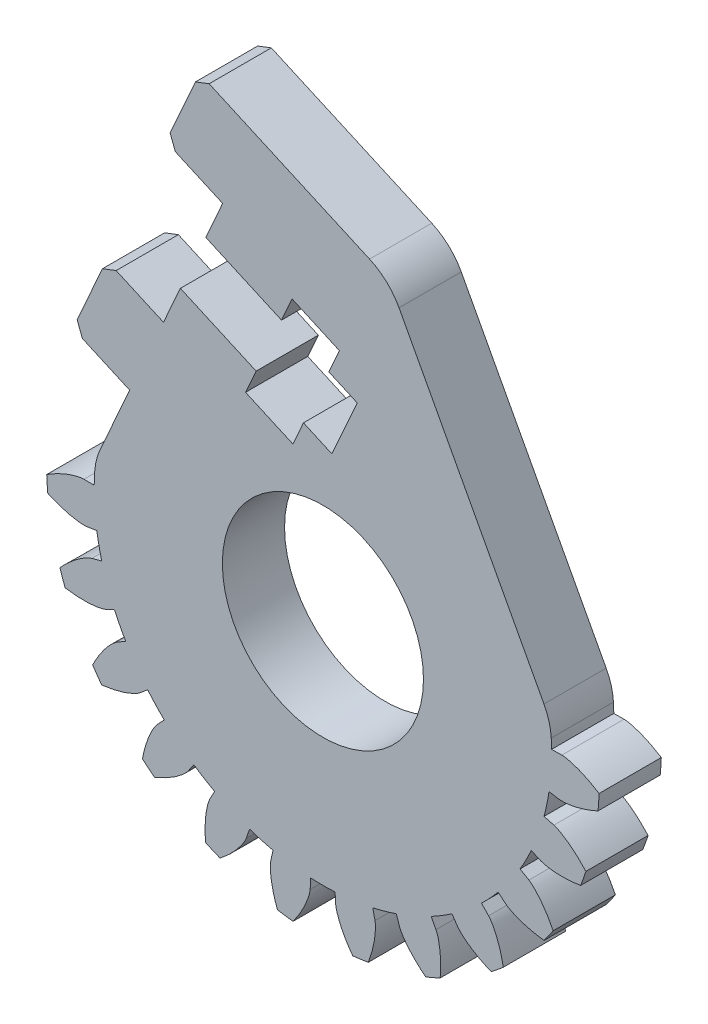
SolidWorks part; units mm, degrees
material "Lasercut ABS"
ref_plane "Front Plane" through (0, 0, 0) normal (0, 0, 1) x (1, 0, 0)
ref_plane "Top Plane" through (0, 0, 0) normal (0, 1, 0) x (1, 0, 0)
ref_plane "Right Plane" through (0, 0, 0) normal (1, 0, 0) x (0, 0, -1)
sketch "Model" plane through (0, 0, 0) normal (0, 0, 1) x (1, 0, 0)
  line L0 (-3.5387, -10.448) -> (-3.6973, -10.9162)
  line L1 (-5.4543, -10.153) -> (-5.2204, -9.7176)
  line L2 (-6.2264, -9.1058) -> (-6.5054, -9.5139)
  line L3 (-7.9913, -8.3049) -> (-7.6486, -7.9488)
  line L4 (-8.4522, -7.0883) -> (-8.8309, -7.4059)
  line L5 (-9.9356, -5.8409) -> (-9.5095, -5.5904)
  line L6 (-10.0512, -4.5451) -> (-10.5016, -4.7487)
  line L7 (-11.1431, -2.9437) -> (-10.6651, -2.8175)
  line L8 (-10.9047, -1.6648) -> (-11.3933, -1.7394)
  line L9 (-11.524, 0.1718) -> (-11.0298, 0.1644)
  line L10 (-10.9495, 1.339) -> (-11.4401, 1.399)
  line L11 (-11.0504, 3.2746) -> (-10.5764, 3.1341)
  line L12 (-10.1822, 4.2435) -> (-10.6384, 4.4336)
  line L13 (-9.7571, 6.1345) -> (-9.3387, 5.8714)
  line L14 (-8.6597, 6.8332) -> (-9.0477, 7.1394)
  line L15 (-7.7402, 8.5394) -> (-7.4083, 8.1732)
  line L16 (-6.495, 8.9162) -> (-6.786, 9.3157)
  line L17 (-5.1493, 10.3111) -> (-4.9285, 9.8688)
  line L18 (-3.8486, 10.3379) -> (-4.021, 10.8011)
  line L19 (-2.1765, 11.318) -> (-2.0831, 10.8326)
  line L20 (-0.9167, 10.9929) -> (-0.9578, 11.4855)
  line L21 (0.9578, 11.4855) -> (0.9167, 10.9929)
  line L22 (2.0831, 10.8326) -> (2.1765, 11.318)
  line L23 (4.021, 10.8011) -> (3.8486, 10.3379)
  line L24 (4.9285, 9.8688) -> (5.1493, 10.3111)
  line L25 (6.786, 9.3157) -> (6.495, 8.9162)
  line L26 (7.4083, 8.1732) -> (7.7402, 8.5394)
  line L27 (9.0477, 7.1394) -> (8.6597, 6.8332)
  line L28 (9.3387, 5.8714) -> (9.7571, 6.1345)
  line L29 (10.6384, 4.4336) -> (10.1822, 4.2435)
  line L30 (10.5764, 3.1341) -> (11.0504, 3.2746)
  line L31 (11.4401, 1.399) -> (10.9495, 1.339)
  line L32 (11.0298, 0.1644) -> (11.524, 0.1718)
  line L33 (11.3933, -1.7394) -> (10.9047, -1.6648)
  line L34 (10.6651, -2.8175) -> (11.1431, -2.9437)
  line L35 (10.5016, -4.7487) -> (10.0512, -4.5451)
  line L36 (9.5095, -5.5904) -> (9.9356, -5.8409)
  line L37 (8.8309, -7.4059) -> (8.4522, -7.0883)
  line L38 (7.6486, -7.9488) -> (7.9913, -8.3049)
  line L39 (6.5054, -9.5139) -> (6.2264, -9.1058)
  line L40 (5.2204, -9.7176) -> (5.4543, -10.153)
  line L41 (3.6973, -10.9162) -> (3.5387, -10.448)
  line L42 (2.405, -10.7657) -> (2.5128, -11.2481)
  line L43 (0.6151, -11.5089) -> (0.5887, -11.0153)
  line L44 (-0.5887, -11.0153) -> (-0.6151, -11.5089)
  line L45 (-2.5128, -11.2481) -> (-2.405, -10.7657)
  arc A0 (-5.6568, -12.0719) -> (-4.9615, -12.3739) centre (0, 0) ccw
  arc A1 (-6.2264, -9.1058) -> (-5.2204, -9.7176) centre (0, 0) ccw
  arc A2 (-8.704, -10.098) -> (-8.1159, -10.5765) centre (0, 0) ccw
  arc A3 (-8.4522, -7.0883) -> (-7.6486, -7.9488) centre (0, 0) ccw
  arc A4 (-11.1057, -7.3752) -> (-10.6684, -7.9946) centre (0, 0) ccw
  arc A5 (-10.0512, -4.5451) -> (-9.5095, -5.5904) centre (0, 0) ccw
  arc A6 (-12.6836, -4.1055) -> (-12.4297, -4.8198) centre (0, 0) ccw
  arc A7 (-10.9047, -1.6648) -> (-10.6651, -2.8175) centre (0, 0) ccw
  arc A8 (-13.3209, -0.5312) -> (-13.2692, -1.2876) centre (0, 0) ccw
  arc A9 (-10.9495, 1.339) -> (-11.0298, 0.1644) centre (0, 0) ccw
  arc A10 (-12.9703, 3.0824) -> (-13.1245, 2.3401) centre (0, 0) ccw
  arc A11 (-10.1822, 4.2435) -> (-10.5764, 3.1341) centre (0, 0) ccw
  arc A12 (-11.6577, 6.4675) -> (-12.0065, 5.7943) centre (0, 0) ccw
  arc A13 (-8.6597, 6.8332) -> (-9.3387, 5.8714) centre (0, 0) ccw
  arc A14 (-9.4805, 9.3728) -> (-9.998, 8.8187) centre (0, 0) ccw
  arc A15 (-6.495, 8.9162) -> (-7.4083, 8.1732) centre (0, 0) ccw
  arc A16 (-6.6002, 11.5831) -> (-7.2479, 11.1891) centre (0, 0) ccw
  arc A17 (-3.8486, 10.3379) -> (-4.9285, 9.8688) centre (0, 0) ccw
  arc A18 (-3.2303, 12.9342) -> (-3.9604, 12.7297) centre (0, 0) ccw
  arc A19 (-0.9167, 10.9929) -> (-2.0831, 10.8326) centre (0, 0) ccw
  arc A20 (0.3791, 13.3261) -> (-0.3791, 13.3261) centre (0, 0) ccw
  arc A21 (2.0831, 10.8326) -> (0.9167, 10.9929) centre (0, 0) ccw
  arc A22 (3.9604, 12.7297) -> (3.2303, 12.9342) centre (0, 0) ccw
  arc A23 (4.9285, 9.8688) -> (3.8486, 10.3379) centre (0, 0) ccw
  arc A24 (7.2479, 11.1891) -> (6.6002, 11.5831) centre (0, 0) ccw
  arc A25 (7.4083, 8.1732) -> (6.495, 8.9162) centre (0, 0) ccw
  arc A26 (9.998, 8.8187) -> (9.4805, 9.3728) centre (0, 0) ccw
  arc A27 (9.3387, 5.8714) -> (8.6597, 6.8332) centre (0, 0) ccw
  arc A28 (12.0065, 5.7943) -> (11.6577, 6.4675) centre (0, 0) ccw
  arc A29 (10.5764, 3.1341) -> (10.1822, 4.2435) centre (0, 0) ccw
  arc A30 (13.1245, 2.3401) -> (12.9703, 3.0824) centre (0, 0) ccw
  arc A31 (11.0298, 0.1644) -> (10.9495, 1.339) centre (0, 0) ccw
  arc A32 (13.2692, -1.2876) -> (13.3209, -0.5312) centre (0, 0) ccw
  arc A33 (10.6651, -2.8175) -> (10.9047, -1.6648) centre (0, 0) ccw
  arc A34 (12.4297, -4.8198) -> (12.6836, -4.1055) centre (0, 0) ccw
  arc A35 (9.5095, -5.5904) -> (10.0512, -4.5451) centre (0, 0) ccw
  arc A36 (10.6684, -7.9946) -> (11.1057, -7.3752) centre (0, 0) ccw
  arc A37 (7.6486, -7.9488) -> (8.4522, -7.0883) centre (0, 0) ccw
  arc A38 (8.1159, -10.5765) -> (8.704, -10.098) centre (0, 0) ccw
  arc A39 (5.2204, -9.7176) -> (6.2264, -9.1058) centre (0, 0) ccw
  arc A40 (4.9615, -12.3739) -> (5.6568, -12.0719) centre (0, 0) ccw
  arc A41 (2.405, -10.7657) -> (3.5387, -10.448) centre (0, 0) ccw
  arc A42 (1.439, -13.2536) -> (2.1901, -13.1504) centre (0, 0) ccw
  arc A43 (-0.5887, -11.0153) -> (0.5887, -11.0153) centre (0, 0) ccw
  arc A44 (-2.1901, -13.1504) -> (-1.439, -13.2536) centre (0, 0) ccw
  arc A45 (-3.5387, -10.448) -> (-2.405, -10.7657) centre (0, 0) ccw
  circle A46 centre (0, 0) radius 12.265 construction
  spline S0 degree 3 poles (-3.6973, -10.9162) (-3.7069, -10.9403) (-3.7475, -11.036) (-3.8652, -11.2386) (-4.0935, -11.5548) (-4.4634, -11.9567) (-4.7761, -12.2317) (-4.9615, -12.3739) knots 34.584629 34.584629 34.584629 34.584629 34.662509 34.896108 35.285436 35.830493 36.531279 36.531279 36.531279 36.531279
  spline S1 degree 3 poles (-5.6568, -12.0719) (-5.6795, -11.8394) (-5.6919, -11.4231) (-5.6506, -10.8784) (-5.5754, -10.4958) (-5.5076, -10.2714) (-5.4654, -10.1765) (-5.4543, -10.153) knots 37.289537 37.289537 37.289537 37.289537 37.990323 38.535379 38.924707 39.158307 39.236186 39.236186 39.236186 39.236186
  spline S2 degree 3 poles (-6.5054, -9.5139) (-6.5211, -9.5345) (-6.586, -9.6157) (-6.754, -9.779) (-7.0591, -10.0219) (-7.5237, -10.3091) (-7.8991, -10.4896) (-8.1159, -10.5765) knots 41.402696 41.402696 41.402696 41.402696 41.480575 41.714175 42.103503 42.648559 43.349345 43.349345 43.349345 43.349345
  spline S3 degree 3 poles (-8.704, -10.098) (-8.6631, -9.868) (-8.5627, -9.4638) (-8.376, -8.9505) (-8.2003, -8.6023) (-8.0746, -8.4046) (-8.0083, -8.3246) (-7.9913, -8.3049) knots 44.107603 44.107603 44.107603 44.107603 44.808389 45.353446 45.742774 45.976373 46.054253 46.054253 46.054253 46.054253
  spline S4 degree 3 poles (-8.8309, -7.4059) (-8.8517, -7.4216) (-8.936, -7.4822) (-9.1419, -7.5942) (-9.5012, -7.7457) (-10.0261, -7.8969) (-10.4362, -7.9695) (-10.6684, -7.9946) knots 48.220763 48.220763 48.220763 48.220763 48.298642 48.532242 48.921569 49.466626 50.167412 50.167412 50.167412 50.167412
  spline S5 degree 3 poles (-11.1057, -7.3752) (-11.0042, -7.1648) (-10.7985, -6.8027) (-10.4802, -6.3587) (-10.2171, -6.0709) (-10.0427, -5.9144) (-9.9573, -5.8552) (-9.9356, -5.8409) knots 50.92567 50.92567 50.92567 50.92567 51.626456 52.171513 52.56084 52.79444 52.87232 52.87232 52.87232 52.87232
  spline S6 degree 3 poles (-10.5016, -4.7487) (-10.5257, -4.7582) (-10.6233, -4.7938) (-10.8518, -4.8461) (-11.2386, -4.8951) (-11.7849, -4.8991) (-12.1993, -4.8583) (-12.4297, -4.8198) knots 55.038829 55.038829 55.038829 55.038829 55.116709 55.350309 55.739636 56.284693 56.985479 56.985479 56.985479 56.985479
  spline S7 degree 3 poles (-12.6836, -4.1055) (-12.5292, -3.9302) (-12.2334, -3.637) (-11.8072, -3.2954) (-11.4762, -3.0892) (-11.266, -2.9856) (-11.1678, -2.9517) (-11.1431, -2.9437) knots 57.743737 57.743737 57.743737 57.743737 58.444523 58.98958 59.378907 59.612507 59.690386 59.690386 59.690386 59.690386
  spline S8 degree 3 poles (-11.3933, -1.7394) (-11.4192, -1.7419) (-11.5228, -1.7499) (-11.7568, -1.7386) (-12.1426, -1.6814) (-12.6696, -1.5379) (-13.0577, -1.3868) (-13.2692, -1.2876) knots 61.856896 61.856896 61.856896 61.856896 61.934776 62.168375 62.557703 63.102759 63.803546 63.803546 63.803546 63.803546
  spline S9 degree 3 poles (-13.3209, -0.5312) (-13.1249, -0.4042) (-12.761, -0.2016) (-12.2584, 0.0123) (-11.8841, 0.1216) (-11.6537, 0.1646) (-11.55, 0.1708) (-11.524, 0.1718) knots 64.561804 64.561804 64.561804 64.561804 65.26259 65.807646 66.196974 66.430574 66.508453 66.508453 66.508453 66.508453
  spline S10 degree 3 poles (-11.4401, 1.399) (-11.4657, 1.4035) (-11.5676, 1.4238) (-11.7899, 1.4978) (-12.1459, 1.657) (-12.6147, 1.9374) (-12.9476, 2.1876) (-13.1245, 2.3401) knots 68.674963 68.674963 68.674963 68.674963 68.752842 68.986442 69.37577 69.920826 70.621612 70.621612 70.621612 70.621612
  spline S11 degree 3 poles (-12.9703, 3.0824) (-12.7472, 3.1519) (-12.3422, 3.2487) (-11.8005, 3.3192) (-11.4106, 3.3233) (-11.1772, 3.3026) (-11.0756, 3.2806) (-11.0504, 3.2746) knots 71.37987 71.37987 71.37987 71.37987 72.080656 72.625713 73.015041 73.24864 73.32652 73.32652 73.32652 73.32652
  spline S12 degree 3 poles (-10.6384, 4.4336) (-10.6618, 4.4449) (-10.7545, 4.4919) (-10.9486, 4.6231) (-11.2485, 4.8724) (-11.6242, 5.2689) (-11.8773, 5.5997) (-12.0065, 5.7943) knots 75.493029 75.493029 75.493029 75.493029 75.570909 75.804509 76.193836 76.738893 77.439679 77.439679 77.439679 77.439679
  spline S13 degree 3 poles (-11.6577, 6.4675) (-11.4242, 6.4742) (-11.008, 6.4581) (-10.4674, 6.3798) (-10.0908, 6.2786) (-9.8716, 6.1957) (-9.7798, 6.1471) (-9.7571, 6.1345) knots 78.197937 78.197937 78.197937 78.197937 78.898723 79.44378 79.833107 80.066707 80.144586 80.144586 80.144586 80.144586
  spline S14 degree 3 poles (-9.0477, 7.1394) (-9.0673, 7.1566) (-9.1438, 7.2268) (-9.2953, 7.4056) (-9.5168, 7.7266) (-9.7716, 8.2097) (-9.9261, 8.5965) (-9.998, 8.8187) knots 82.311096 82.311096 82.311096 82.311096 82.388976 82.622575 83.011903 83.55696 84.257746 84.257746 84.257746 84.257746
  spline S15 degree 3 poles (-9.4805, 9.3728) (-9.2538, 9.3163) (-8.8574, 9.1886) (-8.358, 8.9673) (-8.0227, 8.7683) (-7.834, 8.6293) (-7.7586, 8.5577) (-7.7402, 8.5394) knots 85.016004 85.016004 85.016004 85.016004 85.71679 86.261846 86.651174 86.884774 86.962653 86.962653 86.962653 86.962653
  spline S16 degree 3 poles (-6.786, 9.3157) (-6.8002, 9.3375) (-6.8549, 9.4258) (-6.9526, 9.6388) (-7.0793, 10.0076) (-7.1943, 10.5416) (-7.2387, 10.9557) (-7.2479, 11.1891) knots 89.129163 89.129163 89.129163 89.129163 89.207042 89.440642 89.82997 90.375026 91.075812 91.075812 91.075812 91.075812
  spline S17 degree 3 poles (-6.6002, 11.5831) (-6.3972, 11.4675) (-6.0499, 11.2375) (-5.6287, 10.8897) (-5.3595, 10.6076) (-5.2153, 10.4229) (-5.1621, 10.3337) (-5.1493, 10.3111) knots 91.83407 91.83407 91.83407 91.83407 92.534856 93.079913 93.469241 93.70284 93.78072 93.78072 93.78072 93.78072
  spline S18 degree 3 poles (-4.021, 10.8011) (-4.0288, 10.8259) (-4.0577, 10.9257) (-4.0943, 11.1572) (-4.1167, 11.5465) (-4.0834, 12.0917) (-4.0144, 12.5024) (-3.9604, 12.7297) knots 95.947229 95.947229 95.947229 95.947229 96.025109 96.258709 96.648036 97.193093 97.893879 97.893879 97.893879 97.893879
  spline S19 degree 3 poles (-3.2303, 12.9342) (-3.0661, 12.7682) (-2.7937, 12.4531) (-2.482, 12.0045) (-2.2989, 11.6602) (-2.2099, 11.4435) (-2.1827, 11.3432) (-2.1765, 11.318) knots 98.652137 98.652137 98.652137 98.652137 99.352923 99.89798 100.287307 100.520907 100.598787 100.598787 100.598787 100.598787
  spline S20 degree 3 poles (-0.9578, 11.4855) (-0.9586, 11.5114) (-0.9595, 11.6153) (-0.9323, 11.8481) (-0.8489, 12.229) (-0.6697, 12.745) (-0.4925, 13.1219) (-0.3791, 13.3261) knots 102.765296 102.765296 102.765296 102.765296 102.843176 103.076775 103.466103 104.01116 104.711946 104.711946 104.711946 104.711946
  spline S21 degree 3 poles (0.3791, 13.3261) (0.4925, 13.1219) (0.6697, 12.745) (0.8489, 12.229) (0.9323, 11.8481) (0.9595, 11.6153) (0.9586, 11.5114) (0.9578, 11.4855) knots 105.470204 105.470204 105.470204 105.470204 106.17099 106.716046 107.105374 107.338974 107.416853 107.416853 107.416853 107.416853
  spline S22 degree 3 poles (2.1765, 11.318) (2.1827, 11.3432) (2.2099, 11.4435) (2.2989, 11.6602) (2.482, 12.0045) (2.7937, 12.4531) (3.0661, 12.7682) (3.2303, 12.9342) knots 109.583363 109.583363 109.583363 109.583363 109.661242 109.894842 110.28417 110.829226 111.530012 111.530012 111.530012 111.530012
  spline S23 degree 3 poles (3.9604, 12.7297) (4.0144, 12.5024) (4.0834, 12.0917) (4.1167, 11.5465) (4.0943, 11.1572) (4.0577, 10.9257) (4.0288, 10.8259) (4.021, 10.8011) knots 112.28827 112.28827 112.28827 112.28827 112.989057 113.534113 113.923441 114.15704 114.23492 114.23492 114.23492 114.23492
  spline S24 degree 3 poles (5.1493, 10.3111) (5.1621, 10.3337) (5.2153, 10.4229) (5.3595, 10.6076) (5.6287, 10.8897) (6.0499, 11.2375) (6.3972, 11.4675) (6.6002, 11.5831) knots 116.40143 116.40143 116.40143 116.40143 116.479309 116.712909 117.102236 117.647293 118.348079 118.348079 118.348079 118.348079
  spline S25 degree 3 poles (7.2479, 11.1891) (7.2387, 10.9557) (7.1943, 10.5416) (7.0793, 10.0076) (6.9526, 9.6388) (6.8549, 9.4258) (6.8002, 9.3375) (6.786, 9.3157) knots 119.106337 119.106337 119.106337 119.106337 119.807123 120.35218 120.741507 120.975107 121.052987 121.052987 121.052987 121.052987
  spline S26 degree 3 poles (7.7402, 8.5394) (7.7586, 8.5577) (7.834, 8.6293) (8.0227, 8.7683) (8.358, 8.9673) (8.8574, 9.1886) (9.2538, 9.3163) (9.4805, 9.3728) knots 123.219496 123.219496 123.219496 123.219496 123.297376 123.530976 123.920303 124.46536 125.166146 125.166146 125.166146 125.166146
  spline S27 degree 3 poles (9.998, 8.8187) (9.9261, 8.5965) (9.7716, 8.2097) (9.5168, 7.7266) (9.2953, 7.4056) (9.1438, 7.2268) (9.0673, 7.1566) (9.0477, 7.1394) knots 125.924404 125.924404 125.924404 125.924404 126.62519 127.170247 127.559574 127.793174 127.871053 127.871053 127.871053 127.871053
  spline S28 degree 3 poles (9.7571, 6.1345) (9.7798, 6.1471) (9.8716, 6.1957) (10.0908, 6.2786) (10.4674, 6.3798) (11.008, 6.4581) (11.4242, 6.4742) (11.6577, 6.4675) knots 130.037563 130.037563 130.037563 130.037563 130.115443 130.349042 130.73837 131.283426 131.984213 131.984213 131.984213 131.984213
  spline S29 degree 3 poles (12.0065, 5.7943) (11.8773, 5.5997) (11.6242, 5.2689) (11.2485, 4.8724) (10.9486, 4.6231) (10.7545, 4.4919) (10.6618, 4.4449) (10.6384, 4.4336) knots 132.742471 132.742471 132.742471 132.742471 133.443257 133.988313 134.377641 134.611241 134.68912 134.68912 134.68912 134.68912
  spline S30 degree 3 poles (11.0504, 3.2746) (11.0756, 3.2806) (11.1772, 3.3026) (11.4106, 3.3233) (11.8005, 3.3192) (12.3422, 3.2487) (12.7472, 3.1519) (12.9703, 3.0824) knots 136.85563 136.85563 136.85563 136.85563 136.933509 137.167109 137.556437 138.101493 138.802279 138.802279 138.802279 138.802279
  spline S31 degree 3 poles (13.1245, 2.3401) (12.9476, 2.1876) (12.6147, 1.9374) (12.1459, 1.657) (11.7899, 1.4978) (11.5676, 1.4238) (11.4657, 1.4035) (11.4401, 1.399) knots 139.560537 139.560537 139.560537 139.560537 140.261323 140.80638 141.195708 141.429307 141.507187 141.507187 141.507187 141.507187
  spline S32 degree 3 poles (11.524, 0.1718) (11.55, 0.1708) (11.6537, 0.1646) (11.8841, 0.1216) (12.2584, 0.0123) (12.761, -0.2016) (13.1249, -0.4042) (13.3209, -0.5312) knots 143.673696 143.673696 143.673696 143.673696 143.751576 143.985176 144.374503 144.91956 145.620346 145.620346 145.620346 145.620346
  spline S33 degree 3 poles (13.2692, -1.2876) (13.0577, -1.3868) (12.6696, -1.5379) (12.1426, -1.6814) (11.7568, -1.7386) (11.5228, -1.7499) (11.4192, -1.7419) (11.3933, -1.7394) knots 146.378604 146.378604 146.378604 146.378604 147.07939 147.624447 148.013774 148.247374 148.325254 148.325254 148.325254 148.325254
  spline S34 degree 3 poles (11.1431, -2.9437) (11.1678, -2.9517) (11.266, -2.9856) (11.4762, -3.0892) (11.8072, -3.2954) (12.2334, -3.637) (12.5292, -3.9302) (12.6836, -4.1055) knots 150.491763 150.491763 150.491763 150.491763 150.569643 150.803242 151.19257 151.737627 152.438413 152.438413 152.438413 152.438413
  spline S35 degree 3 poles (12.4297, -4.8198) (12.1993, -4.8583) (11.7849, -4.8991) (11.2386, -4.8951) (10.8518, -4.8461) (10.6233, -4.7938) (10.5257, -4.7582) (10.5016, -4.7487) knots 153.196671 153.196671 153.196671 153.196671 153.897457 154.442513 154.831841 155.065441 155.14332 155.14332 155.14332 155.14332
  spline S36 degree 3 poles (9.9356, -5.8409) (9.9573, -5.8552) (10.0427, -5.9144) (10.2171, -6.0709) (10.4802, -6.3587) (10.7985, -6.8027) (11.0042, -7.1648) (11.1057, -7.3752) knots 157.30983 157.30983 157.30983 157.30983 157.387709 157.621309 158.010637 158.555693 159.256479 159.256479 159.256479 159.256479
  spline S37 degree 3 poles (10.6684, -7.9946) (10.4362, -7.9695) (10.0261, -7.8969) (9.5012, -7.7457) (9.1419, -7.5942) (8.936, -7.4822) (8.8517, -7.4216) (8.8309, -7.4059) knots 160.014737 160.014737 160.014737 160.014737 160.715523 161.26058 161.649908 161.883507 161.961387 161.961387 161.961387 161.961387
  spline S38 degree 3 poles (7.9913, -8.3049) (8.0083, -8.3246) (8.0746, -8.4046) (8.2003, -8.6023) (8.376, -8.9505) (8.5627, -9.4638) (8.6631, -9.868) (8.704, -10.098) knots 164.127897 164.127897 164.127897 164.127897 164.205776 164.439376 164.828703 165.37376 166.074546 166.074546 166.074546 166.074546
  spline S39 degree 3 poles (8.1159, -10.5765) (7.8991, -10.4896) (7.5237, -10.3091) (7.0591, -10.0219) (6.754, -9.779) (6.586, -9.6157) (6.5211, -9.5345) (6.5054, -9.5139) knots 166.832804 166.832804 166.832804 166.832804 167.53359 168.078647 168.467974 168.701574 168.779454 168.779454 168.779454 168.779454
  spline S40 degree 3 poles (5.4543, -10.153) (5.4654, -10.1765) (5.5076, -10.2714) (5.5754, -10.4958) (5.6506, -10.8784) (5.6919, -11.4231) (5.6795, -11.8394) (5.6568, -12.0719) knots 170.945963 170.945963 170.945963 170.945963 171.023843 171.257442 171.64677 172.191827 172.892613 172.892613 172.892613 172.892613
  spline S41 degree 3 poles (4.9615, -12.3739) (4.7761, -12.2317) (4.4634, -11.9567) (4.0935, -11.5548) (3.8652, -11.2386) (3.7475, -11.036) (3.7069, -10.9403) (3.6973, -10.9162) knots 173.650871 173.650871 173.650871 173.650871 174.351657 174.896713 175.286041 175.519641 175.59752 175.59752 175.59752 175.59752
  spline S42 degree 3 poles (2.5128, -11.2481) (2.5172, -11.2737) (2.5322, -11.3765) (2.5369, -11.6108) (2.5061, -11.9995) (2.3989, -12.5351) (2.2746, -12.9326) (2.1901, -13.1504) knots 177.76403 177.76403 177.76403 177.76403 177.841909 178.075509 178.464837 179.009893 179.710679 179.710679 179.710679 179.710679
  spline S43 degree 3 poles (1.439, -13.2536) (1.2989, -13.0667) (1.072, -12.7175) (0.8242, -12.2307) (0.6897, -11.8647) (0.6311, -11.6378) (0.6178, -11.5347) (0.6151, -11.5089) knots 180.468937 180.468937 180.468937 180.468937 181.169724 181.71478 182.104108 182.337707 182.415587 182.415587 182.415587 182.415587
  spline S44 degree 3 poles (-0.6151, -11.5089) (-0.6178, -11.5347) (-0.6311, -11.6378) (-0.6897, -11.8647) (-0.8242, -12.2307) (-1.072, -12.7175) (-1.2989, -13.0667) (-1.439, -13.2536) knots 184.582097 184.582097 184.582097 184.582097 184.659976 184.893576 185.282903 185.82796 186.528746 186.528746 186.528746 186.528746
  spline S45 degree 3 poles (-2.1901, -13.1504) (-2.2746, -12.9326) (-2.3989, -12.5351) (-2.5061, -11.9995) (-2.5369, -11.6108) (-2.5322, -11.3765) (-2.5172, -11.2737) (-2.5128, -11.2481) knots 187.287004 187.287004 187.287004 187.287004 187.98779 188.532847 188.922174 189.155774 189.233654 189.233654 189.233654 189.233654
extrude "Boss-Extrude1" add sketch "Model" along normal blind 3
sketch "Sketch3" plane through (0, 0, 0) normal (0, 0, 1) x (1, 0, 0)
  line L0 (0, 0) -> (-14.8891, 1.8208)
  line L1 (0, 0) -> (14.8891, 1.8208)
  arc A0 (-14.8891, 1.8208) -> (14.8891, 1.8208) centre (0, 0) cw
  dimension "D1" = 15
extrude "Cut-Extrude2" cut sketch "Sketch3" along normal through all
sketch "Sketch4" plane through (0, 0, 0) normal (0, 0, 1) x (1, 0, 0)
  line L0 (0, 0) -> (0, -24.5308) construction
  line L1 (0, -24.5308) -> (9.1314, -4.0765) construction
  line L2 (9.1314, -4.0765) -> (0, 0) construction
  line L3 (0, 0) -> (-10.9495, 1.339) construction
  line L4 (0, 0) -> (10.9495, 1.339) construction
  line L5 (0, 0) -> (-10.9495, 1.339)
  line L6 (0, 0) -> (10.9495, 1.339)
  line L7 (-10.9495, 1.339) -> (-9.3189, 4.9916)
  line L8 (-9.3189, 4.9916) -> (-12.0583, 6.2145)
  line L9 (-12.0583, 6.2145) -> (-10.4277, 9.8671)
  line L10 (-10.4277, 9.8671) -> (-7.6883, 8.6441)
  line L11 (-7.6883, 8.6441) -> (-6.873, 10.4704)
  line L12 (-6.873, 10.4704) -> (-3.2204, 8.8398)
  line L13 (-3.2204, 8.8398) -> (-3.73, 7.6984)
  line L14 (-3.73, 7.6984) -> (-1.4471, 6.6792)
  line L15 (-1.4471, 6.6792) -> (-0.9376, 7.8207)
  line L16 (-0.9376, 7.8207) -> (0.4321, 7.2092)
  line L17 (0.4321, 7.2092) -> (1.6551, 9.9486)
  line L18 (1.6551, 9.9486) -> (0.2854, 10.5601)
  line L19 (0.2854, 10.5601) -> (0.795, 11.7015)
  line L20 (0.795, 11.7015) -> (-1.4879, 12.7206)
  line L21 (-1.4879, 12.7206) -> (-1.9975, 11.5792)
  line L22 (-1.9975, 11.5792) -> (-5.65, 13.2098)
  line L23 (-5.65, 13.2098) -> (-4.8347, 15.0361)
  line L24 (-4.8347, 15.0361) -> (-7.5741, 16.259)
  line L25 (-7.5741, 16.259) -> (-5.9435, 19.9116)
  line L26 (-5.9435, 19.9116) -> (3.1879, 15.8351)
  line L27 (10.9495, 1.339) -> (3.1879, 15.8351)
  dimension "D1" = 10
  dimension "D2" = 22.4
  dimension "D3" = 3
  dimension "D4" = 4
  dimension "D5" = 4
  dimension "D6" = 2
  dimension "D7" = 3
  dimension "D8" = 2
  dimension "D9" = 4
  dimension "D10" = 5.5
  dimension "D11" = 11
  dimension "D12" = 4
  dimension "D13" = 2.5
  dimension "D14" = 10
extrude "Boss-Extrude2" add sketch "Sketch4" along normal up to surface (3 mm away) up to face at (-0.0565, -6.9619, 3)
sketch "Sketch5" plane through (0, 0, 0) normal (0, 0, 1) x (1, 0, 0)
  circle A0 centre (0, 0) radius 4.85
  dimension "D1" = 9.7
extrude "Cut-Extrude3" cut sketch "Sketch5" along normal through all
fillet "Fillet1" radius 3 3 edges at (3.1879, 15.8351, 1.5) (10.9495, 1.339, 1.5) (-10.9495, 1.339, 1.5)
chamfer "Chamfer1" distance 0.5 angle 45 4 edges at (-5.9435, 19.9116, 1.5) (-7.5741, 16.259, 1.5) (-10.4277, 9.8671, 1.5) (-12.0583, 6.2145, 1.5)
sketch "Sketch6" plane through (0, 0, 3) normal (0, 0, 1) x (1, 0, 0)
  line L0 (1.6551, 9.9486) -> (0.4321, 7.2092) construction
  line L1 (-3.73, 7.6984) -> (-3.2204, 8.8398) construction
  arc A0 (-4.9629, 4.9365) -> (0.3352, 6.992) centre (0, 0) ccw construction
  text T0 "E5  ONO V2" font "1CamBam_Stick_3" height 2.5
  dimension "D1" = 7
